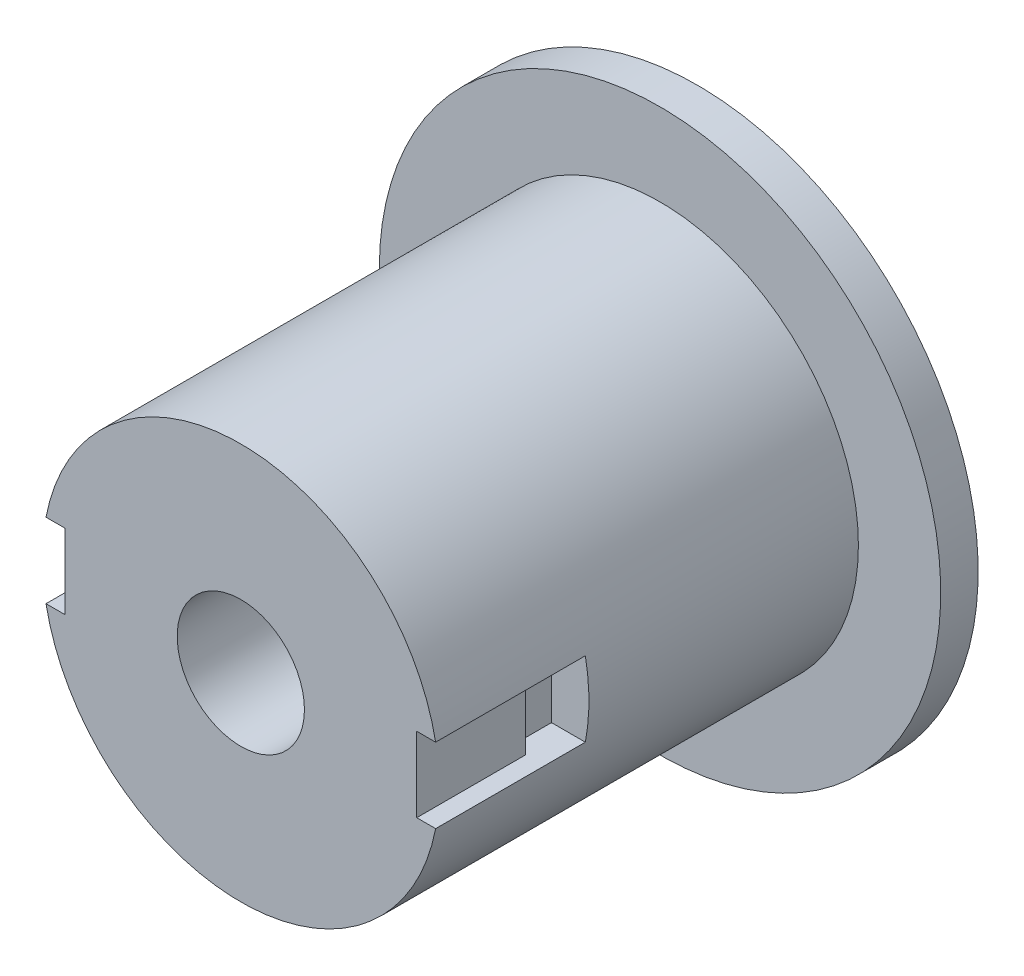
SolidWorks part; units mm, degrees
ref_plane "Front" through (0, 0, 0) normal (0, 0, 1) x (1, 0, 0)
ref_plane "Top" through (0, 0, 0) normal (0, 1, 0) x (1, 0, 0)
ref_plane "Right" through (0, 0, 0) normal (1, 0, 0) x (0, 0, -1)
sketch "Sketch1" plane through (0, 0, 0) normal (0, 0, 1) x (1, 0, 0)
  circle A0 centre (0, 0) radius 26.5
  dimension "D1" = 53
extrude "Boss-Extrude1" add sketch "Sketch1" along normal blind 56
sketch "Sketch4" plane through (0, 0, 0) normal (0, 0, -1) x (-1, 0, 0)
  circle A0 centre (0, 0) radius 37.5
  dimension "D1" = 75
extrude "Boss-Extrude2" add sketch "Sketch4" along normal blind 5
sketch "Sketch5" plane through (0, 0, 56) normal (0, 0, 1) x (1, 0, 0)
  circle A0 centre (0, 0) radius 8.5
  dimension "D1" = 17
extrude "Cut-Extrude1" cut sketch "Sketch5" against normal through all
sketch "Sketch6" plane through (0, 0, 0) normal (0, 1, 0) x (1, 0, 0)
  line L0 (23.5, -56) -> (26.5, -56)
  line L1 (26.5, -56) -> (26.5, -36)
  line L2 (26.5, -56) -> (26.5, 0) construction
  line L3 (26.5, -36) -> (21.5, -36)
  line L4 (21.5, -36) -> (21.5, -39.5)
  line L5 (21.5, -39.5) -> (23.5, -41.5)
  line L6 (23.5, -41.5) -> (23.5, -56)
  point P0 (0, 0)
  dimension "D1" = 135
  dimension "D2" = 3
  dimension "D3" = 5
  dimension "D4" = 20
  dimension "D5" = 3.5
extrude "Cut-Extrude2" cut sketch "Sketch6" against normal blind 5 and the other way blind 5
mirror "Mirror1" about plane through (0, 0, 0) normal (1, 0, 0) of "Cut-Extrude2"
